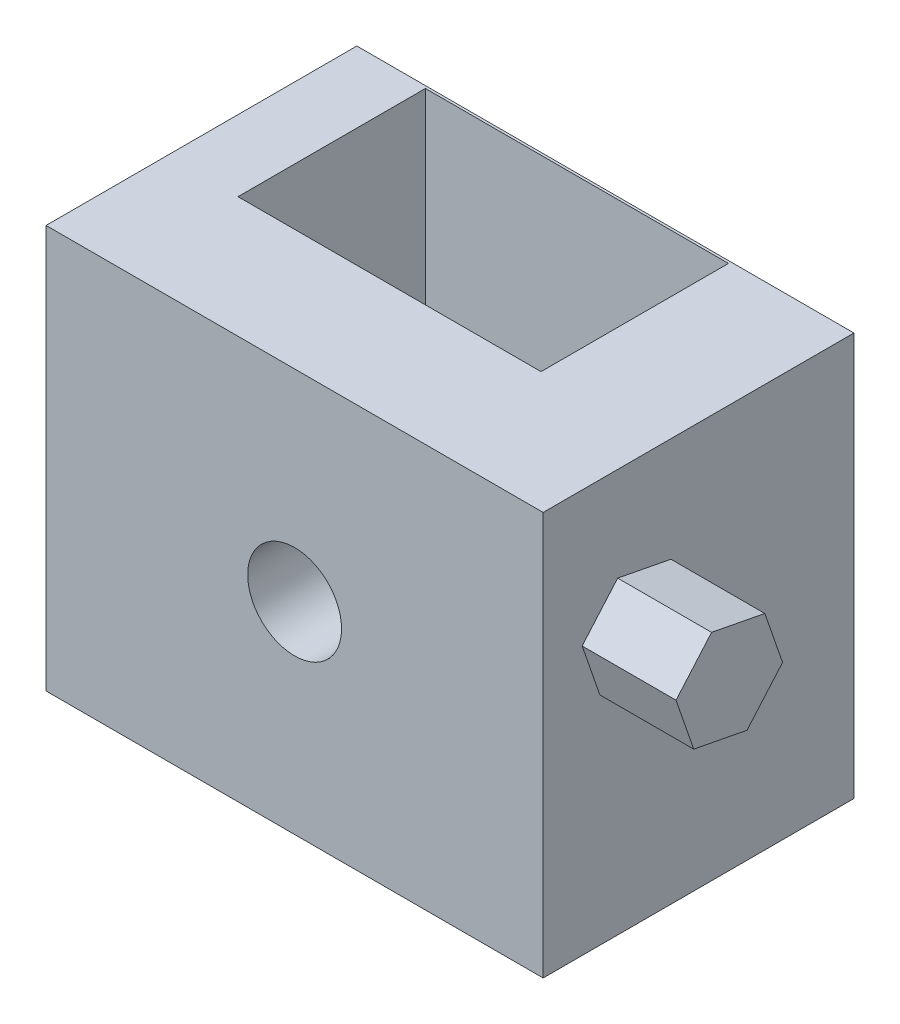
SolidWorks part; units mm, degrees
ref_plane "Front Plane" through (0, 0, 0) normal (0, 0, 1) x (1, 0, 0)
ref_plane "Top Plane" through (0, 0, 0) normal (0, 1, 0) x (1, 0, 0)
ref_plane "Right Plane" through (0, 0, 0) normal (1, 0, 0) x (0, 0, -1)
sketch "Sketch2" plane through (0, 0, 0) normal (0, 0, 1) x (1, 0, 0)
  line L1 (-67.2388, -54.5382) -> (67.2388, -54.5382)
  line L2 (-67.2388, -54.5382) -> (-67.2388, 54.5382)
  line L3 (-67.2388, 54.5382) -> (67.2388, 54.5382)
  line L4 (67.2388, -54.5382) -> (67.2388, 54.5382)
  line L5 (-67.2388, -54.5382) -> (67.2388, 54.5382) construction
  line L6 (-67.2388, 54.5382) -> (67.2388, -54.5382) construction
  point P0 (0, 0)
extrude "Boss-Extrude1" add sketch "Sketch2" along normal blind 84.074
sketch "Sketch3" plane through (0, 0, 84.074) normal (0, 0, 1) x (1, 0, 0)
  circle A0 centre (0, 0) radius 12.7
  dimension "D1" = 25.4
extrude "Cut-Extrude1" cut sketch "Sketch3" against normal blind 127
sketch "Sketch4" plane through (0, 54.5382, 0) normal (0, 1, 0) x (1, 0, 0)
  line L1 (-48.013, -0.6681) -> (33.9651, -0.6681)
  line L2 (-48.013, -0.6681) -> (-48.013, -51.3752)
  line L3 (-48.013, -51.3752) -> (33.9651, -51.3752)
  line L4 (33.9651, -0.6681) -> (33.9651, -51.3752)
extrude "Cut-Extrude2" cut sketch "Sketch4" against normal blind 104.14
sketch "Sketch5" plane through (67.2388, 0, 0) normal (1, 0, 0) x (0, 0, -1)
  line L1 (-54.3263, 1.3258) -> (-44.7111, 12.412)
  line L2 (-44.7111, 12.412) -> (-49.5045, 26.2821)
  line L3 (-49.5045, 26.2821) -> (-63.913, 29.066)
  line L4 (-63.913, 29.066) -> (-73.5282, 17.9798)
  line L5 (-73.5282, 17.9798) -> (-68.7349, 4.1097)
  line L6 (-68.7349, 4.1097) -> (-54.3263, 1.3258)
  circle A0 centre (-59.1197, 15.1959) radius 12.7089 construction
extrude "Boss-Extrude2" add sketch "Sketch5" along normal blind 25.4
